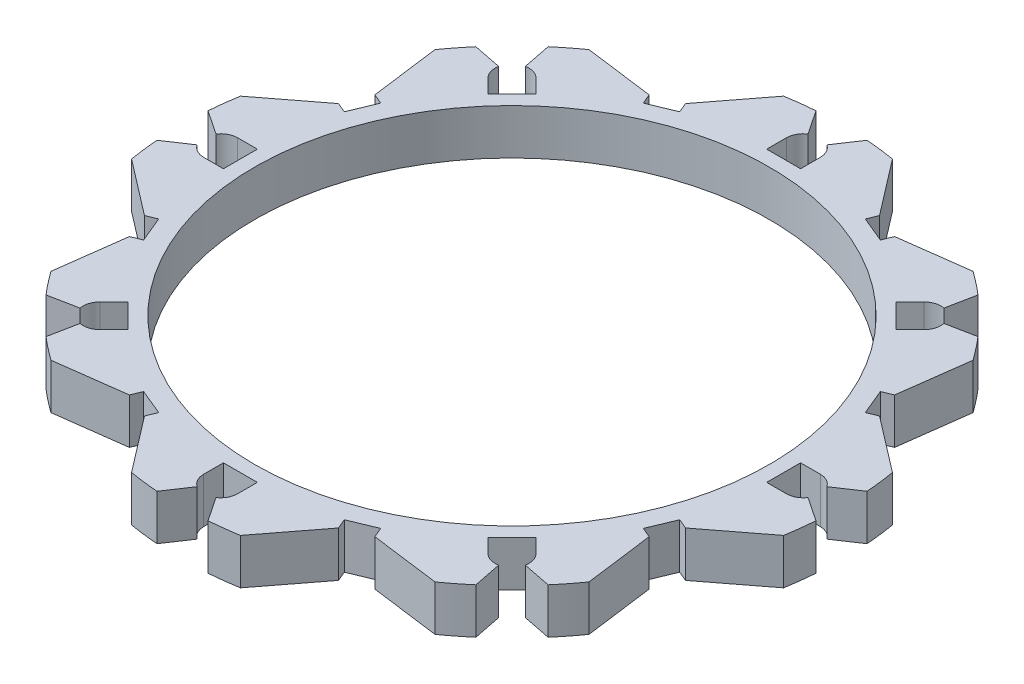
SolidWorks part; units mm, degrees
ref_plane "Front Plane" through (0, 0, 0) normal (0, 0, 1) x (1, 0, 0)
ref_plane "Top Plane" through (0, 0, 0) normal (0, 1, 0) x (1, 0, 0)
ref_plane "Right Plane" through (0, 0, 0) normal (1, 0, 0) x (0, 0, -1)
sketch "Sketch1" plane through (0, 0, 0) normal (0, 1, 0) x (1, 0, 0)
  circle A0 centre (0, 0) radius 54.55
extrude "Boss-Extrude1" add sketch "Sketch1" along normal blind 7.5
sketch "Sketch2" plane through (0, 7.5, 0) normal (0, 1, 0) x (1, 0, 0)
  circle A0 centre (0, 0) radius 42.5
extrude "Cut-Extrude1" cut sketch "Sketch2" against normal through all
sketch "Sketch3" plane through (0, 7.5, 0) normal (0, 1, 0) x (1, 0, 0)
  line L2 (-2.8, -48.082) -> (-2.8, -44.832)
  line L3 (-2.8, -44.832) -> (2.8, -44.832)
  line L4 (2.8, -48.082) -> (2.8, -44.832)
  line L7 (-1.5556, -50.4101) -> (-4.2129, -54.3871)
  line L8 (1.5556, -50.4101) -> (4.2129, -54.3871)
  circle A1 centre (0, 0) radius 54.55 construction
  arc A2 (-2.8, -48.082) -> (-1.5556, -50.4101) centre (0, -48.082) ccw
  arc A3 (1.5556, -50.4101) -> (2.8, -48.082) centre (0, -48.082) ccw
  arc A4 (-4.2129, -54.3871) -> (4.2129, -54.3871) centre (0, 0) ccw
  dimension "D1" = 5.6
  dimension "D2" = 3.25
  dimension "D4" = 3.25
  dimension "D6" = 67.5
extrude "Cut-Extrude2" cut sketch "Sketch3" against normal through all
sketch "Sketch4" plane through (0, 7.5, 0) normal (0, 1, 0) x (-1, 0, 0)
  line L0 (2.75, 48.082) -> (-2.75, 48.082)
  line L1 (2.75, 48.082) -> (2.75, 44.882)
  line L2 (-2.75, 48.082) -> (-2.75, 44.882)
  line L3 (2.75, 44.882) -> (-2.75, 44.882)
  line L4 (2.75, 48.082) -> (-2.75, 44.882) construction
  line L5 (-2.75, 48.082) -> (2.75, 44.882) construction
  line L6 (-2.8, 44.832) -> (2.8, 44.832) construction
  line L7 (0, 0) -> (0, 46.482)
  line L8 (0, 0) -> (20.8754, 50.3976) construction
  arc A0 (-2.1, 48.082) -> (2.1, 48.082) centre (0, 48.082) cw
  point P1 (0, 46.482)
  dimension "D4" = 2.1
  dimension "D1" = 46.482
  dimension "D2" = 5.5
  dimension "D3" = 3.2
  dimension "D5" = 0.05
  dimension "D6" = 22.5
ref_axis "Axis1" through (0, 10.8722, 0) along (0, -1, 0)
sketch "Sketch7" plane through (0, 7.5, 0) normal (0, 1, 0) x (1, 0, 0)
  line L0 (0, 0) -> (-20.8754, -50.3976)
  line L1 (-20.1919, -42.868) -> (-16.0344, -44.5901)
  line L2 (-20.1919, -42.868) -> (-19.5413, -41.2974)
  line L3 (-16.0344, -44.5901) -> (-15.3839, -43.0195)
  line L4 (-19.5413, -41.2974) -> (-15.3839, -43.0195)
  line L5 (-20.1919, -42.868) -> (-15.3839, -43.0195) construction
  line L6 (-16.0344, -44.5901) -> (-19.5413, -41.2974) construction
  line L7 (0, 0) -> (0, -46.482) construction
  arc A1 (-16.7259, -44.3037) -> (-19.5004, -43.1544) centre (-18.1132, -43.7291) cw
  point P7 (-17.7879, -42.9438)
  dimension "D1" = 46.482
  dimension "D2" = 4.5
  dimension "D3" = 1.7
  dimension "D4" = 22.5
sketch "Sketch9" plane through (0, 7.5, 0) normal (0, 1, 0) x (1, 0, 0)
  line L4 (-20.2572, -42.8951) -> (-31.6909, -44.4004)
  line L5 (-16.0074, -44.6554) -> (-8.987, -53.8046)
  line L6 (0, 0) -> (-20.8754, -50.3976) construction
  line L8 (-19.5684, -41.2321) -> (-20.2572, -42.8951)
  line L9 (-20.2572, -42.8951) -> (-16.0074, -44.6554)
  line L10 (-16.0074, -44.6554) -> (-15.3186, -42.9924)
  line L11 (-15.3186, -42.9924) -> (-19.5684, -41.2321)
  line L12 (-19.5684, -41.2321) -> (-20.2572, -42.8951)
  line L14 (-16.0074, -44.6554) -> (-15.3186, -42.9924)
  line L15 (-15.3186, -42.9924) -> (-19.5684, -41.2321)
  arc A0 (4.2129, -54.3871) -> (-4.2129, -54.3871) centre (0, 0) ccw construction
  arc A1 (-31.6909, -44.4004) -> (-8.987, -53.8046) centre (0, 0) ccw
  dimension "D2" = 60
  dimension "D3" = 60
  dimension "D1" = 0.05
extrude "Cut-Extrude6" cut sketch "Sketch9" against normal through all
pattern_circular "CirPattern1" count 8 over 360 about axis through (0, 10.8722, 0) along (0, -1, 0) of "Cut-Extrude2"
pattern_circular "CirPattern2" count 8 over 360 about axis through (0, 10.8722, 0) along (0, -1, 0) of "Cut-Extrude6"
ref_plane "Plane1" through (0, 0, 0) normal (0.9239, 0, -0.3827) x (-0.3827, 0, -0.9239)
